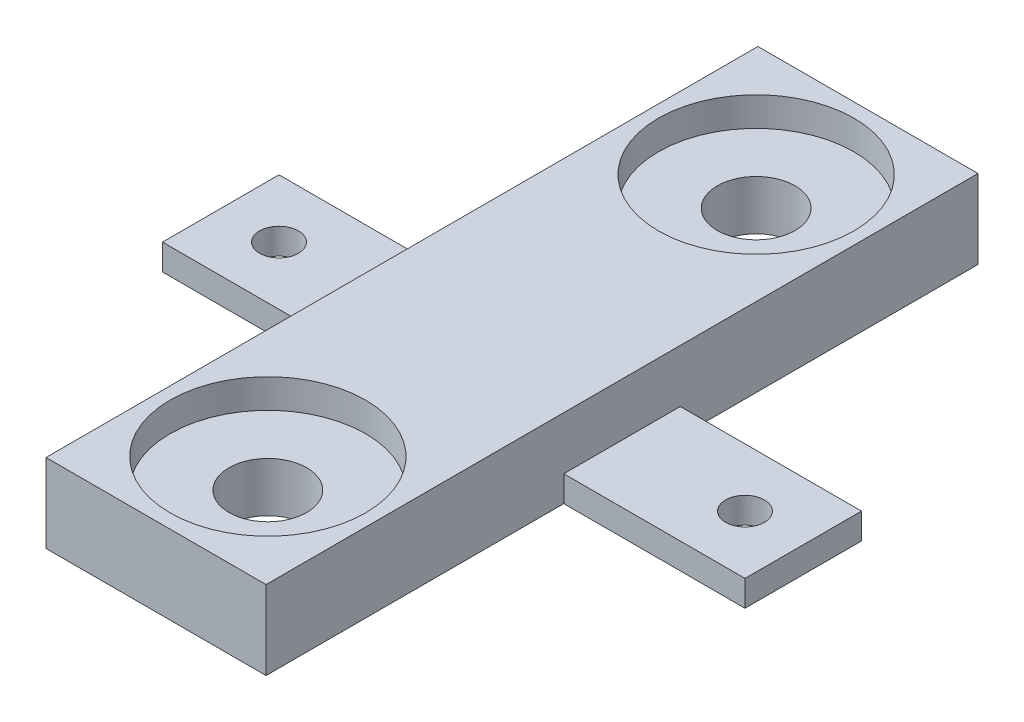
SolidWorks part; units mm, degrees
material "Nylon 101"
ref_plane "Front Plane" through (0, 0, 0) normal (0, 0, 1) x (1, 0, 0)
ref_plane "Top Plane" through (0, 0, 0) normal (0, 1, 0) x (1, 0, 0)
ref_plane "Right Plane" through (0, 0, 0) normal (1, 0, 0) x (0, 0, -1)
sketch "Sketch1" plane through (0, 0, 0) normal (0, 1, 0) x (1, 0, 0)
  line L0 (0, -18.8625) -> (0, -27.5) construction
  line L1 (-8.5, 27.5) -> (8.5, 27.5)
  line L2 (-8.5, 27.5) -> (-8.5, -27.5)
  line L3 (-8.5, -27.5) -> (8.5, -27.5)
  line L4 (8.5, 27.5) -> (8.5, -27.5)
  line L5 (-8.5, 0) -> (0, 0) construction
  line L6 (0, 18.8625) -> (0, -18.8625) construction
  line L7 (-18, 0) -> (18, 0) construction
  line L8 (-8.5, 4.5) -> (-22.5, 4.5)
  line L9 (-8.5, 4.5) -> (-8.5, -4.5)
  line L10 (-8.5, -4.5) -> (-22.5, -4.5)
  line L11 (-22.5, 4.5) -> (-22.5, -4.5)
  line L12 (8.5, 4.5) -> (22.5, 4.5)
  line L13 (8.5, 4.5) -> (8.5, -4.5)
  line L14 (8.5, -4.5) -> (22.5, -4.5)
  line L15 (22.5, 4.5) -> (22.5, -4.5)
  circle A0 centre (0, 18.8625) radius 7.55
  circle A1 centre (0, -18.8625) radius 7.55
  circle A2 centre (-18, 0) radius 1.5
  circle A3 centre (18, 0) radius 1.5
  point P24 (0, 0)
  point P26 (0, 0)
  point P28 (-22.5, 0)
  dimension "D3" = 15.1
  dimension "D7" = 3
  dimension "D1" = 55
  dimension "D2" = 17
  dimension "D4" = 37.725
  dimension "D6" = 36
  dimension "D8" = 4.5
  dimension "D9" = 9
extrude "Boss-Extrude1" add sketch "Sketch1" along normal blind 2 contours L4 L1 L2 L3 A1 A0 | L15 L12 L4 L14 A3 | L8 L11 L10 L2 A2 | A1 | A0 region at (0, 0, 0) region at (-15.3514, 0, 0) region at (15.3514, 0, 0) region at (0, 0, -18.8625) region at (0, 0, 18.8625)
extrude "Boss-Extrude2" add sketch "Sketch1<4>" along normal blind 1.838 from surface contours L4 L1 L2 L3 A1 A0 | A1 | A0 region at (0, 0, 0) region at (0, 0, -18.8625) region at (0, 0, 18.8625) starting at face at (0, 2, 0)
sketch "Sketch1<4>" plane through (0, 0, 0) normal (0, 1, 0) x (1, 0, 0) same geometry as "Sketch1"
extrude "Boss-Extrude3" add sketch "Sketch1<5>" along normal blind 2.25 from surface contours L4 L1 L2 L3 A1 A0 region at (0, 0, 0) starting at face at (0, 3.838, 0)
sketch "Sketch1<5>" plane through (0, 0, 0) normal (0, 1, 0) x (1, 0, 0) same geometry as "Sketch1"
sketch "Sketch3" plane through (0, 0, 0) normal (0, -1, 0) x (1, 0, 0)
  circle A0 centre (0, -18.8625) radius 3
  circle A1 centre (0, 18.8625) radius 3
  circle A2 centre (0, 18.8625) radius 7.55 construction
  dimension "D1" = 6
extrude "Cut-Extrude1" cut sketch "Sketch3" against normal through all
equation "\"D1@Boss-Extrude2\"=\"bottomThickness\"-2.25mm-1.5mm"
equation "\"bottomThickness\"= .220in"
equation "\"wallThickness\"= .125in"
